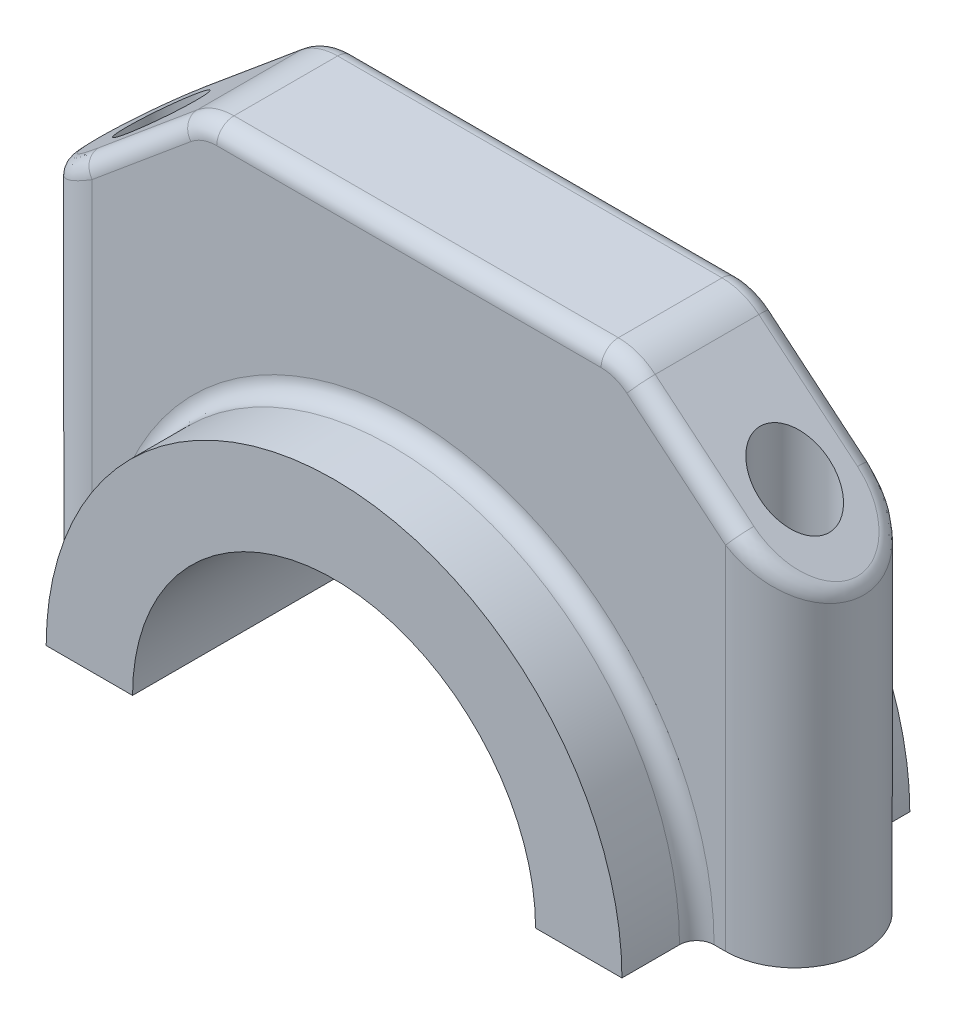
SolidWorks part; units mm, degrees
ref_plane "前视基准面" through (0, 0, 0) normal (0, 0, 1) x (1, 0, 0)
ref_plane "上视基准面" through (0, 0, 0) normal (0, 1, 0) x (1, 0, 0)
ref_plane "右视基准面" through (0, 0, 0) normal (1, 0, 0) x (0, 0, -1)
other "Configuration Table"
sketch "草图1" plane through (0, 0, 0) normal (0, 0, 1) x (1, 0, 0)
  line L0 (-50, 0) -> (-35, 0)
  line L1 (35, 0) -> (50, 0)
  arc A0 (35, 0) -> (-35, 0) centre (0, 0) ccw
  arc A1 (50, 0) -> (-50, 0) centre (0, 0) ccw
extrude "凸台-拉伸3" add sketch "草图1" along normal mid plane 50
ref_plane "基准面2" through (0, 80, 0) normal (0, -1, 0) x (-1, 0, 0)
sketch "草图6" plane through (0, 80, 0) normal (0, -1, 0) x (-1, 0, 0)
  line L0 (-55, 0) -> (55, 0) construction
  line L1 (-55, 12) -> (55, 12)
  line L2 (-55, -12) -> (55, -12)
  arc A0 (-55, 12) -> (-55, -12) centre (-55, 0) ccw
  arc A1 (55, -12) -> (55, 12) centre (55, 0) ccw
  point P3 (0, 0)
  dimension "D2" = 12
  dimension "D1" = 110
extrude "凸台-拉伸4" add sketch "草图6" along normal up to surface (80 mm away) up to face at (-42.5, 0, 0)
sketch "草图7" plane through (0, 0, 12) normal (0, 0, 1) x (1, 0, 0)
  line L1 (-35, 0) -> (35, 0)
  line L2 (-35, 0) -> (35, 0)
  arc A1 (35, 0) -> (-35, 0) centre (0, 0) ccw
  arc A2 (35, 0) -> (-35, 0) centre (0, 0) ccw
  dimension "D1" = 0
extrude "切除-拉伸4" cut sketch "草图7" against normal through all
sketch "草图8" plane through (0, 0, 0) normal (0, -1, 0) x (1, 0, 0)
  circle A0 centre (-55, 0) radius 6
  circle A1 centre (55, 0) radius 6
extrude "切除-拉伸5" cut sketch "草图8" against normal through all
sketch "草图9" plane through (0, 0, 0) normal (0, 0, 1) x (1, 0, 0)
  line L0 (-67, 55) -> (-67, 80)
  line L1 (-67, 80) -> (-67, 0) construction
  line L2 (-17.6, 80) -> (17.6, 80) construction
  line L3 (-67, 80) -> (-37, 80)
  line L4 (-37, 80) -> (-67, 55)
  line L5 (0, 0) -> (0, 86.7163) construction
  line L6 (37, 80) -> (67, 55)
  line L7 (67, 80) -> (37, 80)
  line L8 (67, 55) -> (67, 80)
  dimension "D1" = 25
  dimension "D2" = 30
extrude "切除-拉伸6" cut sketch "草图9" against normal through all both and the other way through all
fillet "圆角1" radius 10 2 edges at (-37, 80, 0) (37, 80, 0)
fillet "圆角2" radius 3 14 edges at (-36.7838, 79.4027, -12) (-47.3907, 71.3411, -12) (-67, 55, 0) (-47.3907, 71.3411, 12) (-36.7838, 79.4027, 12) (0, 80, 12) (36.7838, 79.4027, 12) (47.3907, 71.3411, 12) (67, 55, 0) (47.3907, 71.3411, -12) (36.7838, 79.4027, -12) (0, 80, -12) (0, 50, -12) (0, 50, 12)
